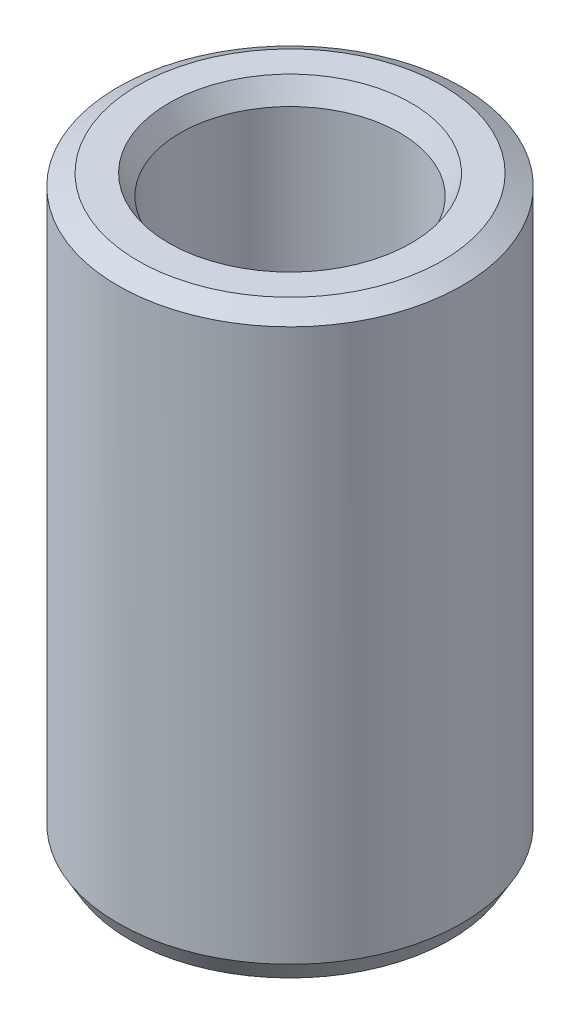
SolidWorks part; units mm, degrees
ref_plane "Front Plane" through (0, 0, 0) normal (0, 0, 1) x (1, 0, 0)
ref_plane "Top Plane" through (0, 0, 0) normal (0, 1, 0) x (1, 0, 0)
ref_plane "Right Plane" through (0, 0, 0) normal (1, 0, 0) x (0, 0, -1)
sketch "Sketch1" plane through (0, 0, 0) normal (0, 1, 0) x (1, 0, 0)
  circle A0 centre (0, 0) radius 25
  dimension "SLEEVE_OD" = 50
extrude "Boss-Extrude1" add sketch "Sketch1" along normal blind 84.8044
sketch "Sketch2" plane through (0, 0, 0) normal (0, 1, 0) x (1, 0, 0)
  circle A0 centre (0, 0) radius 15.9476
  dimension "BORE_D" = 31.8952
extrude "Cut-Extrude1" cut sketch "Sketch2" along normal through all
chamfer "Chamfer1" distance 1.6753 angle 60 4 edges at (0, 84.8044, 15.9476) (0, 0, 15.9476) (0, 0, 25) (0, 84.8044, 25) first distance on face at (0, 84.8044, 15.9476) first distance on face at (0, 0, 15.9476) first distance on face at (0, 84.8044, 25)
